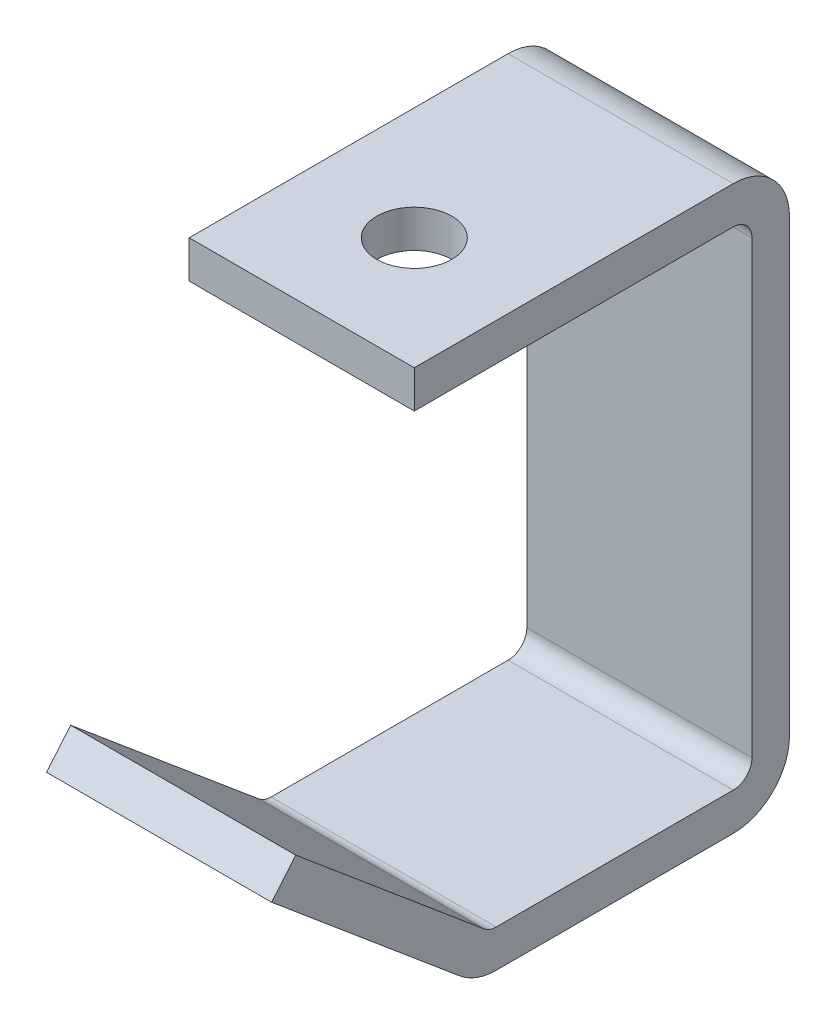
SolidWorks part; units mm, degrees
material "1023 Carbon Steel Sheet (SS)"
ref_plane "Front" through (0, 0, 0) normal (0, 0, 1) x (1, 0, 0)
ref_plane "Top" through (0, 0, 0) normal (0, 1, 0) x (-1, 0, 0)
ref_plane "Right" through (0, 0, 0) normal (1, 0, 0) x (0, 0, -1)
sketch "Sketch1" plane through (0, 0, 0) normal (1, 0, 0) x (0, 0, -1)
  line L0 (-57.15, 82.55) -> (0, 82.55)
  line L1 (-57.15, 82.55) -> (-57.15, 51.3934)
  line L2 (0, 82.55) -> (0, 0)
  line L3 (-77.209, 27.488) -> (-44.45, 0)
  line L4 (-44.45, 0) -> (0, 0)
  line L5 (-77.209, 27.488) -> (-57.15, 51.3934)
  dimension "D1" = 40
  dimension "D2" = 82.55
  dimension "D3" = 44.45
  dimension "D4" = 42.7638
  dimension "D5" = 57.15
extrude "Boss-Extrude1" add sketch "Sketch1" along normal mid plane 38.1
shell "Shell1" thickness 6.35
fillet "Fillet1" radius 3.175 3 edges at (0, 0, 0) (0, 82.55, 0) (0, 0, 44.45)
fillet "Fillet2" radius 9.525 3 edges at (0, -6.35, 46.7612) (0, -6.35, -6.35) (0, 88.9, -6.35)
sketch "Sketch2" plane through (0, 88.9, 0) normal (0, 1, 0) x (-1, 0, 0)
  line L0 (-19.05, 57.15) -> (19.05, 57.15) construction
  circle A0 centre (0, 38.1) radius 6.35
  point P4 (0, 57.15)
  dimension "D1" = 12.7
  dimension "D2" = 19.05
extrude "Cut-Extrude1" cut sketch "Sketch2" against normal up to next
